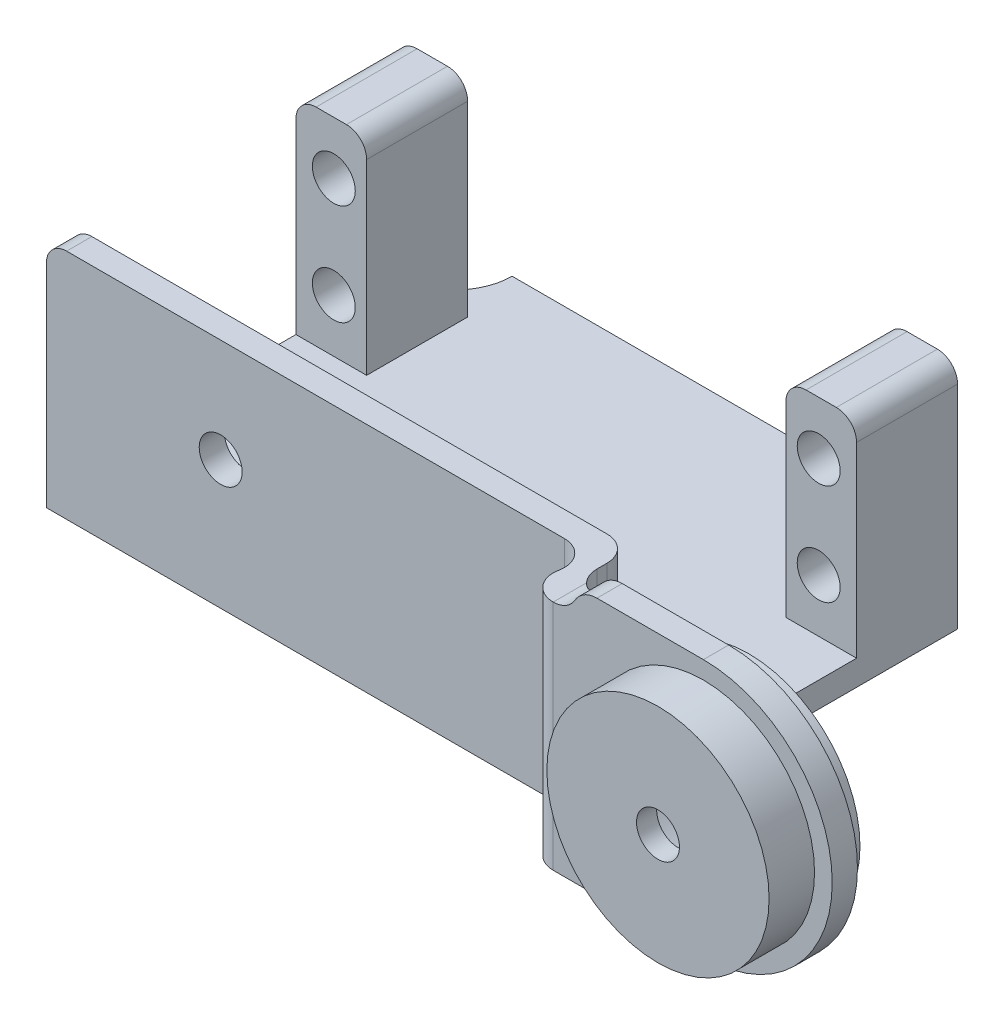
SolidWorks part; units mm, degrees
ref_plane "Front" through (0, 0, 0) normal (0, 0, 1) x (1, 0, 0)
ref_plane "Top" through (0, 0, 0) normal (0, 1, 0) x (1, 0, 0)
ref_plane "Right" through (0, 0, 0) normal (1, 0, 0) x (0, 0, -1)
sketch "Sketch1" plane through (0, 0, 0) normal (0, 1, 0) x (1, 0, 0)
  line L1 (0, 0) -> (55.5, 0)
  line L2 (0, 0) -> (0, 37.9)
  line L3 (0, 37.9) -> (55.5, 37.9)
  line L4 (55.5, 0) -> (55.5, 37.9)
  dimension "D1" = 37.9
  dimension "D2" = 55.5
extrude "bracketBase" add sketch "Sketch1" along normal blind 2.5
ref_plane "referencePlane1" through (0, 0, -8.2) normal (0, 0, 1) x (1, 0, 0)
sketch "Sketch2" plane through (0, 0, -8.2) normal (0, 0, 1) x (1, 0, 0)
  line L0 (27.75, 2.5) -> (27.75, 23) construction
  line L1 (0, 2.5) -> (7, 2.5)
  line L2 (0, 2.5) -> (0, 23)
  line L3 (0, 23) -> (7, 23)
  line L4 (7, 2.5) -> (7, 23)
  line L5 (0, 2.5) -> (55.5, 2.5) construction
  line L6 (55.5, 23) -> (48.5, 23)
  line L7 (48.5, 2.5) -> (48.5, 23)
  line L8 (55.5, 2.5) -> (48.5, 2.5)
  line L9 (55.5, 2.5) -> (55.5, 23)
  dimension "D1" = 20.5
  dimension "D2" = 7
extrude "servoMountingHoleTabs" add sketch "Sketch2" along normal blind 2.5
sketch "Sketch3" plane through (0, 0, -5.7) normal (0, 0, 1) x (1, 0, 0)
  line L0 (0, 12.75) -> (7, 12.75) construction
  line L3 (0, 23) -> (0, 2.5) construction
  line L4 (7, 2.5) -> (7, 23) construction
  line L5 (7, 23) -> (0, 23) construction
  line L6 (27.75, 2.5) -> (27.75, 23) construction
  line L7 (0, 2.5) -> (55.5, 2.5) construction
  circle A0 centre (3.75, 17.75) radius 2.125
  circle A1 centre (3.75, 7.75) radius 2.125
  circle A2 centre (51.75, 7.75) radius 2.125
  circle A3 centre (51.75, 17.75) radius 2.125
  dimension "D1" = 4.25
  dimension "D2" = 3.75
  dimension "D3" = 5.25
extrude "servoMountingHoles" cut sketch "Sketch3" against normal blind 2.5
sketch "Sketch4" plane through (0, 0, 0) normal (0, 1, 0) x (1, 0, 0)
  line L0 (55.5, 8.2) -> (55.5, 37.9) construction
  line L1 (0, 37.9) -> (55.5, 37.9)
  line L2 (0, 37.9) -> (0, 40.4)
  line L3 (0, 40.4) -> (55.5, 40.4)
  line L4 (55.5, 37.9) -> (55.5, 40.4)
  dimension "D1" = 2.5
extrude "baseWall" add sketch "Sketch4" along normal up to surface (23 mm away) up to face at (3.5, 23, -6.95)
sketch "Sketch6" plane through (0, 2.5, 0) normal (0, 1, 0) x (1, 0, 0)
  circle A0 centre (0, 0) radius 5.7
  circle A1 centre (55.5, 0) radius 5.7
extrude "baseTrim" cut sketch "Sketch6" against normal blind 2.5
fillet "Fillet1" radius 2 6 edges at (7, 23, -6.95) (48.5, 23, -6.95) (0, 23, -6.95) (55.5, 23, -6.95) (55.5, 23, -39.15) (0, 23, -39.15)
sketch "Sketch7" plane through (0, 0, -40.4) normal (0, 0, -1) x (-1, 0, 0)
  line L0 (0, 21) -> (0, 0) construction
  line L1 (-55.5, 0) -> (0, 0) construction
  circle A0 centre (-17.25, 12.75) radius 2.125
  dimension "D1" = 4.25
  dimension "D2" = 17.25
  dimension "D3" = 12.75
extrude "M4mountingHole" cut sketch "Sketch7" against normal blind 10
sketch "Sketch8" plane through (0, 0, -8.2) normal (0, 0, -1) x (-1, 0, 0)
  line L4 (-48.5, 2.5) -> (-48.5, 21)
  line L5 (-50.5, 23) -> (-53.5, 23)
  line L6 (-55.5, 21) -> (-55.5, 2.5)
  line L7 (-55.5, 2.5) -> (-48.5, 2.5)
  line L8 (-48.5, 2.5) -> (-48.5, 21)
  line L9 (-50.5, 23) -> (-53.5, 23)
  line L10 (-55.5, 21) -> (-55.5, 2.5)
  line L11 (-55.5, 2.5) -> (-48.5, 2.5)
  line L12 (-2, 23) -> (-5, 23)
  line L13 (-7, 21) -> (-7, 2.5)
  line L14 (-7, 2.5) -> (0, 2.5)
  line L15 (0, 2.5) -> (0, 21)
  line L16 (-2, 23) -> (-5, 23)
  line L17 (-7, 21) -> (-7, 2.5)
  line L18 (-7, 2.5) -> (0, 2.5)
  line L19 (0, 2.5) -> (0, 21)
  circle A0 centre (-51.75, 17.75) radius 2.125 construction
  circle A1 centre (-51.75, 17.75) radius 2.125
  arc A2 (-48.5, 21) -> (-50.5, 23) centre (-50.5, 21) ccw
  arc A3 (-53.5, 23) -> (-55.5, 21) centre (-53.5, 21) ccw
  arc A4 (-48.5, 21) -> (-50.5, 23) centre (-50.5, 21) ccw
  arc A5 (-53.5, 23) -> (-55.5, 21) centre (-53.5, 21) ccw
  arc A6 (-5, 23) -> (-7, 21) centre (-5, 21) ccw
  arc A7 (0, 21) -> (-2, 23) centre (-2, 21) ccw
  arc A8 (-5, 23) -> (-7, 21) centre (-5, 21) ccw
  arc A9 (0, 21) -> (-2, 23) centre (-2, 21) ccw
  circle A10 centre (-51.75, 7.75) radius 2.125 construction
  circle A11 centre (-51.75, 7.75) radius 2.125
  circle A12 centre (-3.75, 17.75) radius 2.125 construction
  circle A13 centre (-3.75, 17.75) radius 2.125
  circle A14 centre (-3.75, 7.75) radius 2.125 construction
  circle A15 centre (-3.75, 7.75) radius 2.125
  dimension "D1" = 0
  dimension "D2" = 0
extrude "tabExtension" add sketch "Sketch8" along normal blind 7.5
sketch "Sketch10" plane through (0, 0, 0) normal (0, -1, 0) x (1, 0, 0)
  line L0 (86.5796, -43.8997) -> (55.5, -43.8997)
  line L1 (86.5796, -46.3997) -> (47.5, -46.3997)
  line L2 (86.5796, -43.8997) -> (86.5796, -46.3997)
  line L3 (2, -40.4) -> (53.5, -40.4) construction
  line L4 (55.5, -40.4) -> (55.5, -37.9)
  line L5 (55.5, -43.8997) -> (55.5, -40.4)
  line L7 (47.5, -40.4) -> (47.5, -46.3997)
  line L8 (55.5, -5.7) -> (55.5, -40.4) construction
  line L9 (55.5, -37.9) -> (47.5, -37.9)
  line L10 (47.5, -37.9) -> (47.5, -40.4)
  line L11 (55.5, -37.9) -> (0, -37.9) construction
  dimension "D1" = 31.0796
  dimension "D2" = 39.0796
  dimension "D3" = 2.5
  dimension "D4" = 3.4997
extrude "Boss-Extrude1" add sketch "Sketch10" against normal blind 25.5
ref_plane "Plane1" through (0, 0, -41.8997) normal (0, 0, 1) x (1, 0, 0)
sketch "Sketch12" plane through (0, 0, -41.8997) normal (0, 0, 1) x (1, 0, 0)
  line L0 (55.5, 2.5) -> (55.5, 21) construction
  circle A0 centre (71.0398, 12.75) radius 11
  dimension "D1" = 22
  dimension "D2" = 12.75
  dimension "D3" = 15.5398
extrude "Boss-Extrude2" add sketch "Sketch12" against normal blind 9
sketch "Sketch13" plane through (0, 0, -41.8997) normal (0, 0, 1) x (1, 0, 0)
  circle A0 centre (71.0398, 12.75) radius 9.75
  dimension "D1" = 19.5
extrude "Cut-Extrude1" cut sketch "Sketch13" against normal offset from surface (7 mm away) 2 up to face at (82.0398, 12.75, -50.8997)
sketch "Sketch14" plane through (0, 0, -48.8997) normal (0, 0, 1) x (1, 0, 0)
  circle A0 centre (71.0398, 12.75) radius 2.125
  dimension "D1" = 4.25
extrude "Cut-Extrude2" cut sketch "Sketch14" against normal blind 2
sketch "Sketch15" plane through (47.5, 0, 0) normal (-1, 0, 0) x (0, 0, 1)
  line L0 (-46.3997, 25.5) -> (-46.3997, 0) construction
  line L1 (-37.9, 25.5) -> (-46.3997, 25.5)
  line L2 (-37.9, 25.5) -> (-37.9, 23)
  line L3 (-37.9, 23) -> (-46.3997, 23)
  line L4 (-46.3997, 25.5) -> (-46.3997, 23)
  line L5 (-37.9, 23) -> (-40.4, 23) construction
extrude "Cut-Extrude3" cut sketch "Sketch15" against normal up to surface (8 mm away) up to face at (55.5, 11.1667, -23.5666)
fillet "Fillet2" radius 2.5 2 edges at (47.5, 11.5, -46.3997) (55.5, 12.75, -37.9)
fillet "Fillet4" radius 2.5 2 edges at (55.5, 11.5, -43.8997) (47.5, 11.5, -40.4)
sketch "Sketch16" plane through (0, 0, -43.8997) normal (0, 0, 1) x (1, 0, 0)
  line L0 (86.5796, 25.5) -> (55.5, 25.5) construction
  line L1 (60.5, 25.5) -> (55.5, 25.5)
  line L2 (55.5, 25.5) -> (55.5, 23)
  line L3 (55.5, 23) -> (58, 23)
  arc A0 (58, 23) -> (60.5, 25.5) centre (60.5, 23) cw
extrude "Cut-Extrude4" cut sketch "Sketch16" against normal through all
fillet "Fillet5" radius 2.5 1 edges at (58, 23, -45.1497)
sketch "Sketch17" plane through (0, 0, -43.8997) normal (0, 0, 1) x (1, 0, 0)
  line L0 (71.0398, 0) -> (86.5796, 0)
  line L1 (86.5796, 0) -> (86.5796, 25.5)
  line L2 (86.5796, 25.5) -> (71.0398, 25.5)
  arc A0 (71.0398, 0) -> (71.0398, 25.5) centre (71.0398, 12.75) ccw
extrude "Cut-Extrude5" cut sketch "Sketch17" against normal blind 25
sketch "Sketch18" plane through (0, 23, 0) normal (0, 1, 0) x (1, 0, 0)
  line L0 (45, 40.4) -> (51.2708, 40.4)
  line L1 (56.1699, 46.3997) -> (50, 46.3997) construction
  line L2 (47.5, 43.8997) -> (47.5, 42.9) construction
  line L3 (47.5, 43.8997) -> (47.5, 42.9)
  line L4 (56.1699, 46.3997) -> (50, 46.3997)
  arc A0 (56.1699, 46.3997) -> (53.7204, 43.3998) centre (56.1699, 43.8997) ccw
  arc A1 (53.7204, 43.3998) -> (51.2708, 40.4) centre (51.2708, 42.9) cw
  arc A2 (45, 40.4) -> (47.5, 42.9) centre (45, 42.9) ccw construction
  arc A3 (45, 40.4) -> (47.5, 42.9) centre (45, 42.9) ccw
  arc A4 (50, 46.3997) -> (47.5, 43.8997) centre (50, 43.8997) ccw construction
  arc A5 (50, 46.3997) -> (47.5, 43.8997) centre (50, 43.8997) ccw
  dimension "D1" = 2.5
  dimension "D2" = 2.5
extrude "Cut-Extrude6" cut sketch "Sketch18" against normal through all
ref_plane "Plane2" through (0, 0, 0) normal (0, 0, 1) x (1, 0, 0)
mirror "Mirror1" about plane through (0, 0, 0) normal (0, 0, 1) of bodies 118
sketch "Sketch19" plane through (0, 0, 0) normal (0, 0, 1) x (1, 0, 0)
  line L1 (-62.4263, -47.4109) -> (97.6594, -47.4109)
  line L2 (-62.4263, -47.4109) -> (-62.4263, 69.8749)
  line L3 (-62.4263, 69.8749) -> (97.6594, 69.8749)
  line L4 (97.6594, -47.4109) -> (97.6594, 69.8749)
extrude "Cut-Extrude7" cut sketch "Sketch19" against normal blind 96
